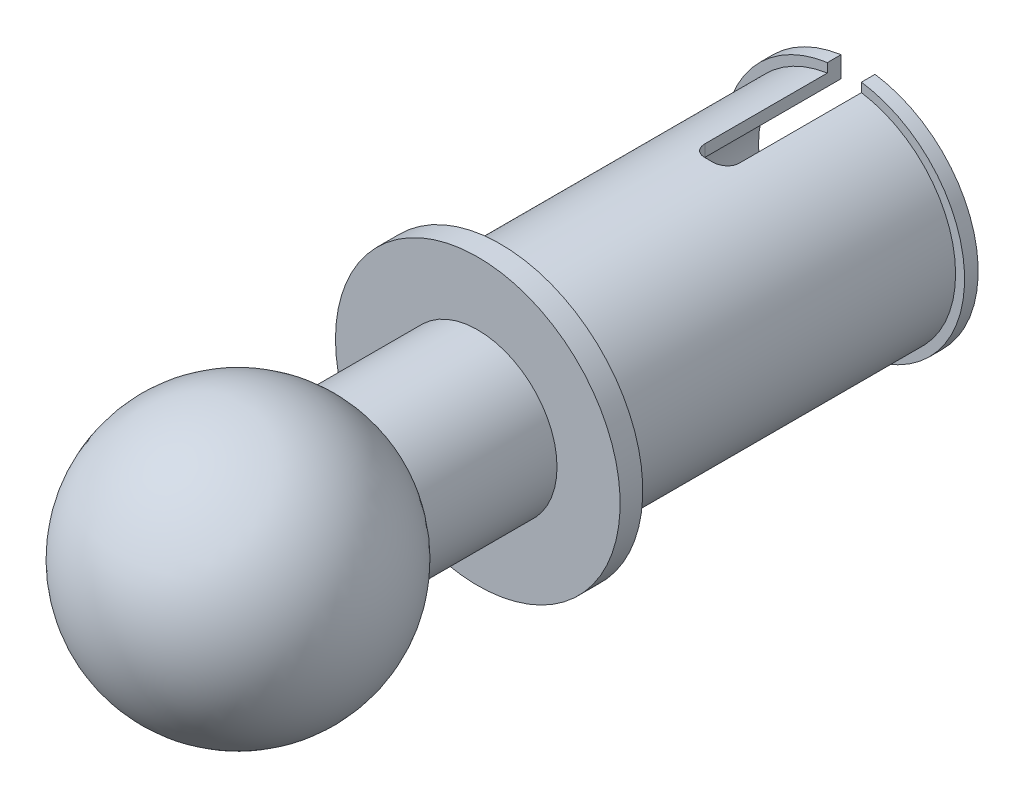
SolidWorks part; units mm, degrees
ref_plane "Front Plane" through (0, 0, 0) normal (0, 0, 1) x (1, 0, 0)
ref_plane "Top Plane" through (0, 0, 0) normal (0, 1, 0) x (1, 0, 0)
ref_plane "Right Plane" through (0, 0, 0) normal (1, 0, 0) x (0, 0, -1)
sketch "Sketch1" plane through (0, 0, 0) normal (0, 0, 1) x (1, 0, 0)
  line L0 (-2.4, 0) -> (2.4, 0)
  line L1 (-2.4, 0.895) -> (-2.4, -0.895)
  line L2 (-2.4, 0.895) -> (-0.9, 0.895)
  line L3 (0, 2.4) -> (0, -2.4)
  line L4 (-0.9, 0.895) -> (-0.9, 2.4)
  line L5 (-0.9, 2.4) -> (0.9, 2.4)
  line L6 (0.9, 0.895) -> (0.9, 2.4)
  line L7 (2.4, 0.895) -> (0.9, 0.895)
  line L8 (2.4, 0.895) -> (2.4, -0.895)
  line L9 (2.4, -0.895) -> (0.9, -0.895)
  line L10 (0.9, -0.895) -> (0.9, -2.4)
  line L11 (-0.9, -2.4) -> (0.9, -2.4)
  line L12 (-0.9, -0.895) -> (-0.9, -2.4)
  line L13 (-2.4, -0.895) -> (-0.9, -0.895)
  point P4 (0, 0)
  point P8 (-2.4, 0)
  point P12 (0, 0)
  dimension "D1" = 4.8
  dimension "D2" = 1.79
  dimension "D3" = 1.5
  dimension "D4" = 4.8
extrude "Boss-Extrude1" add sketch "Sketch1" along normal blind 7.9 contours L5 L4 L2 L1 L0 L3 | L1 L13 L12 L11 L3 L0 | L8 L7 L6 L5 L3 L0 | L3 L11 L10 L9 L8 L0 region at (-2.3661, 0.4475, 0) region at (-1.2, -0.0339, 0) region at (0.0339, 1.2, 0) region at (1.2, -0.0339, 0)
sketch "Sketch2" plane through (0, 0, 0) normal (0, 0, -1) x (-1, 0, 0)
  circle A0 centre (0, 0) radius 3.1445
extrude "Boss-Extrude3" add sketch "Sketch2" along normal blind 0.5 contours A0
sketch "Sketch3" plane through (0, 0, -0.5) normal (0, 0, -1) x (-1, 0, 0)
  circle A0 centre (0, 0) radius 2.4559
  dimension "D1" = 4.9118
extrude "Boss-Extrude4" add sketch "Sketch3" along normal blind 7.9
sketch "Sketch4" plane through (0, 0, -8.4) normal (0, 0, -1) x (-1, 0, 0)
  circle A0 centre (0, 0) radius 2.6546
extrude "Boss-Extrude5" add sketch "Sketch4" against normal blind 0.3
sketch "Sketch5" plane through (0, 0, -8.4) normal (0, 0, -1) x (-1, 0, 0)
  circle A0 centre (0, 0) radius 2.1986
extrude "Cut-Extrude1" cut sketch "Sketch5" against normal up to surface (7.9 mm away) up to face at (-2.4559, 0, -0.5)
sketch "Sketch6" plane through (0, 0, -8.4) normal (0, 0, -1) x (-1, 0, 0)
  line L0 (0, 0) -> (2.6546, 0) construction
  line L1 (0, 0) -> (0, 2.6546) construction
  line L2 (0.3755, 2.6546) -> (0.3755, 2.1663)
  line L3 (0.3755, 2.6546) -> (-0.3755, 2.6546)
  line L4 (0, 2.6546) -> (0, 2.1663)
  line L5 (0.3755, 2.1663) -> (-0.3755, 2.1663)
  line L6 (-0.3755, 2.6546) -> (-0.3755, 2.1663)
  line L7 (0.3755, -2.6546) -> (0.3755, -2.1663)
  line L8 (0.3755, -2.6546) -> (-0.3755, -2.6546)
  line L9 (-0.3755, -2.6546) -> (-0.3755, -2.1663)
  line L10 (0.3755, -2.1663) -> (-0.3755, -2.1663)
  circle A0 centre (0, 0) radius 2.6546 construction
  circle A1 centre (0, 0) radius 2.1986 construction
  circle M8 centre (0, 0) radius 2.1986
  circle M9 centre (0, 0) radius 2.6546
extrude "Cut-Extrude2" cut sketch "Sketch6" against normal blind 3.3 contours L4 L2 M9 M8 | L6 L4 M9 M8 | L9 L7 M9 M8 region at (-0.1881, 2.4168, -8.4) region at (0.1881, 2.4168, -8.4) region at (0, -2.4168, -8.4)
fillet "Fillet1" radius 0.3 4 edges at (-0.3755, -2.2967, -5.1) (0.3755, -2.2967, -5.1) (-0.3755, 2.2967, -5.1) (0.3755, 2.2967, -5.1)
sketch "Sketch7" plane through (0, 0, 0) normal (0, 0, 1) x (1, 0, 0)
  circle A0 centre (0, 0) radius 3.1445
extrude "Cut-Extrude5" cut sketch "Sketch7" along normal blind 9
sketch "Sketch8" plane through (0, 0, 0) normal (0, 0, 1) x (1, 0, 0)
  circle A0 centre (0, 0) radius 1.75
  dimension "D1" = 3.5
extrude "Boss-Extrude6" add sketch "Sketch8" along normal blind 3 contours A0
sketch "Sketch9" plane through (0, 0, 0) normal (1, 0, 0) x (0, 0, -1)
  line L0 (-5.2979, 3.0091) -> (-5.2979, -2.9909)
  arc A0 (-5.2979, -2.9909) -> (-5.2979, 3.0091) centre (-5.2979, 0.0091) ccw
  point P1 (-5.436, 0.0091)
  dimension "D1" = 3
revolve "Revolve1" add sketch "Sketch9" angle 360 about L0
